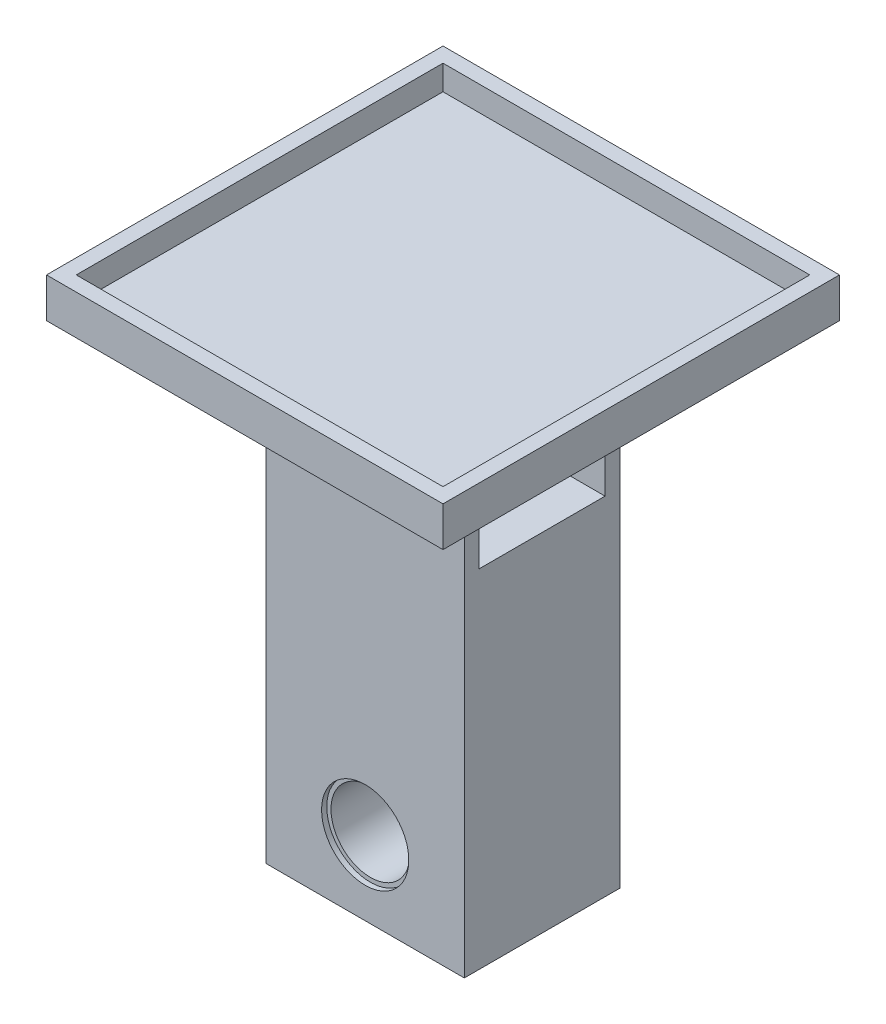
SolidWorks part; units mm, degrees
ref_plane "Front Plane" through (0, 0, 0) normal (0, 0, 1) x (1, 0, 0)
ref_plane "Top Plane" through (0, 0, 0) normal (0, 1, 0) x (1, 0, 0)
ref_plane "Right Plane" through (0, 0, 0) normal (1, 0, 0) x (0, 0, -1)
sketch "Sketch2" plane through (0, 0, 0) normal (0, 0, 1) x (1, 0, 0)
  circle A0 centre (0, 0) radius 7.5
  dimension "D1" = 15
extrude "Boss-Extrude1" add sketch "Sketch2" along normal mid plane 5
sketch "Sketch3" plane through (0, 0, 0) normal (1, 0, 0) x (0, 0, -1)
  line L0 (-15.7, 44.5) -> (-12.7, 44.5)
  line L1 (-12.7, 44.5) -> (-12.7, 17.5)
  line L2 (-12.7, 17.5) -> (12.7, 17.5)
  line L3 (-15.7, 44.5) -> (-15.7, 7.5)
  line L5 (0, 40.7714) -> (0, -28.5595) construction
  line L6 (15.7, 44.5) -> (15.7, 7.5)
  line L7 (12.7, 44.5) -> (12.7, 17.5)
  line L8 (15.7, 44.5) -> (12.7, 44.5)
  line L10 (-15.7, 7.5) -> (-15.7, -52.5)
  line L12 (-15.7, -52.5) -> (15.7, -52.5)
  line L13 (15.7, -52.5) -> (15.7, 7.5)
  line L14 (-2.5, -7.5) -> (2.5, -7.5) construction
  line L15 (2.5, 7.5) -> (-2.5, 7.5) construction
  dimension "D1" = 27
  dimension "D2" = 3
  dimension "D3" = 45
  dimension "D4" = 12.7
  dimension "D5" = 10
extrude "Boss-Extrude3" add sketch "Sketch3" along normal mid plane 40 contours L5 L2 L1 L0 L3 | L5 L10 L12 | L5 L12 L13 | L2 L5 L6 L8 L7 region at (0, -14.1708, 0)
sketch "Sketch4" plane through (0, 0, 15.7) normal (0, 0, 1) x (1, 0, 0)
  line L0 (0, -89.3007) -> (0, 55.521) construction
  line L1 (20, 17.5) -> (-20, 17.5) construction
  circle A0 centre (0, 30.2) radius 3
  dimension "D1" = 6
  dimension "D2" = 12.7
extrude "Cut-Extrude1" cut sketch "Sketch4" against normal up to surface (31.4 mm away) up to face at (0, -4, -15.7)
sketch "Sketch5" plane through (0, 44.5, 0) normal (0, 1, 0) x (1, 0, 0)
  line L0 (40, 40) -> (-40, -40) construction
  line L1 (-40, 40) -> (40, 40)
  line L2 (-40, 40) -> (-40, -40)
  line L3 (-40, -40) -> (40, -40)
  line L4 (40, 40) -> (40, -40)
  point P4 (0, 0)
  dimension "D1" = 80
  dimension "D2" = 80
extrude "Boss-Extrude4" add sketch "Sketch5" along normal blind 3
sketch "Sketch6" plane through (0, 47.5, 0) normal (0, 1, 0) x (1, 0, 0)
  line L0 (37, 37) -> (-37, -37) construction
  line L1 (-37, -37) -> (37, -37)
  line L2 (-37, -37) -> (-37, 37)
  line L3 (-37, 37) -> (37, 37)
  line L4 (37, -37) -> (37, 37)
  line L6 (-40, -40) -> (40, -40)
  line L7 (-40, -40) -> (-40, 40)
  line L8 (-40, 40) -> (40, 40)
  line L9 (40, -40) -> (40, 40)
  line L10 (-40, -40) -> (40, 40) construction
  line L11 (-40, 40) -> (40, -40) construction
  point P4 (0, 0)
  point P6 (0, 0)
  dimension "D1" = 3
  dimension "D2" = 3
extrude "Boss-Extrude5" add sketch "Sketch6" along normal blind 5
sketch "Sketch7" plane through (-20, 0, 0) normal (-1, 0, 0) x (0, 0, 1)
  line L0 (15.7, -52.5) -> (-15.7, -52.5) construction
  line L1 (-10.7, -37.5) -> (10.7, -37.5)
  line L2 (-10.7, -37.5) -> (-10.7, -52.5)
  line L3 (-10.7, -52.5) -> (10.7, -52.5)
  line L4 (10.7, -37.5) -> (10.7, -52.5)
  line L5 (-10.7, -37.5) -> (10.7, -52.5) construction
  line L6 (-10.7, -52.5) -> (10.7, -37.5) construction
  line L7 (15.7, 44.5) -> (15.7, -52.5) construction
  point P0 (0, -45)
  point P10 (0, -45)
  point P11 (0, 0)
  dimension "D1" = 5
  dimension "D2" = 15
extrude "Cut-Extrude2" [suppressed] cut sketch "Sketch7" against normal through all
sketch "Sketch8" plane through (0, 0, -15.7) normal (0, 0, -1) x (-1, 0, 0)
  line L0 (-20, -52.5) -> (20, -52.5) construction
  circle A0 centre (0, -37.5) radius 7.95
  point P2 (0, -2.8216)
  point P5 (3.839, 2.5)
  dimension "D1" = 15.9
  dimension "D2" = 15
extrude "Cut-Extrude3" cut sketch "Sketch8" against normal through all
sketch "Sketch9" plane through (0, 0, -15.7) normal (0, 0, -1) x (-1, 0, 0)
  circle A0 centre (0, -37.5) radius 8.8
  dimension "D1" = 17.6
extrude "Cut-Extrude4" cut sketch "Sketch9" against normal blind 1.05
mirror "Mirror1" about plane through (0, 0, 0) normal (0, 0, 1) of "Cut-Extrude4"
